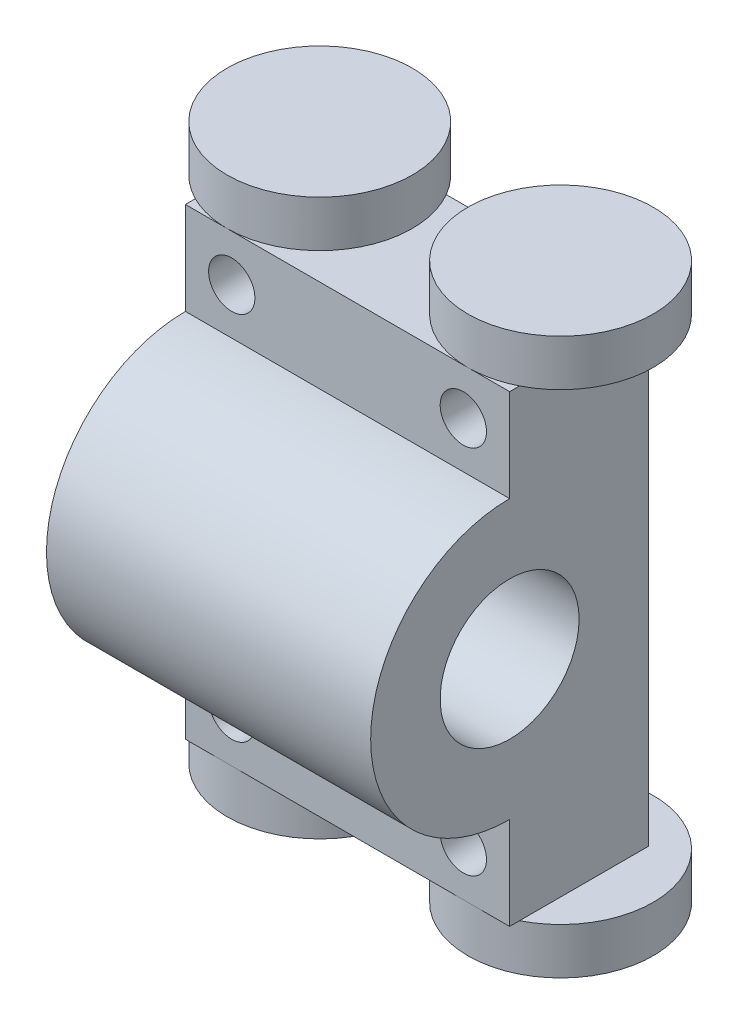
SolidWorks part; units mm, degrees
ref_plane "Front Plane" through (0, 0, 0) normal (0, 0, 1) x (1, 0, 0)
ref_plane "Top Plane" through (0, 0, 0) normal (0, 1, 0) x (1, 0, 0)
ref_plane "Right Plane" through (0, 0, 0) normal (1, 0, 0) x (0, 0, -1)
sketch "Sketch1" plane through (0, 0, 0) normal (1, 0, 0) x (0, 0, -1)
  line L5 (0, 0) -> (-30, 0) construction
  line L6 (-15, -15) -> (-15, -25)
  line L7 (-15, 25) -> (0, 25)
  line L8 (-15, 25) -> (-15, 15)
  line L9 (-15, -25) -> (0, -25)
  line L10 (0, 25) -> (0, -25)
  arc A0 (-15, 15) -> (-15, -15) centre (-15, 0) ccw
  point P0 (0, 0)
  point P1 (-29.8834, 0)
  point P2 (-15, -14.9995)
  point P3 (-15, -9.8928)
  point P9 (-32.7876, 0)
  point P15 (-28.8274, 0)
  point P16 (0, 0)
  dimension "D1" = 15
  dimension "D2" = 50
  dimension "D3" = 15
extrude "body" add sketch "Sketch1" along normal blind 35
sketch "Sketch3" plane through (35, 0, 0) normal (1, 0, 0) x (0, 0, -1)
  circle A0 centre (-15, 0) radius 7.5
  arc A1 (-15, 15) -> (-15, -15) centre (-15, 0) ccw construction
  dimension "D1" = 15
extrude "shaft hole" cut sketch "Sketch3" against normal blind 40
sketch "Sketch4" plane through (0, 25, 0) normal (0, 1, 0) x (1, 0, 0)
  line L0 (17.5, -15) -> (17.5, -6.3939) construction
  line L3 (35, 0) -> (0, 0) construction
  circle A0 centre (4.5, -5) radius 2.5
  circle A1 centre (30.5, -5) radius 2.5
  point P6 (0, 0)
  point P9 (17.5, 0)
  point P10 (7.2598, -4.9505)
  point P11 (7.5, -14.6293)
  point P12 (17.5, -6.3939)
  dimension "D1" = 5
  dimension "D2" = 26
  dimension "D3" = 5
extrude "Boss-Extrude1" add sketch "Sketch4" along normal blind 5
mirror "Mirror1" about plane through (0, 0, 0) normal (0, 1, 0) of "Boss-Extrude1"
sketch "Sketch5" plane through (0, 30, 0) normal (0, 1, 0) x (1, 0, 0)
  circle A0 centre (4.5, -5) radius 10
  dimension "D1" = 20
extrude "bearing" add sketch "Sketch5" against normal blind 5
mirror "Mirror2" about plane through (0, 0, 0) normal (0, 1, 0) of "bearing"
ref_plane "Plane1" through (17.5, 0, 0) normal (1, 0, 0) x (0, 0, -1)
mirror "Mirror5" about plane through (17.5, 0, 0) normal (1, 0, 0) of "bearing", "Mirror2"
sketch "Sketch6" plane through (0, 0, 15) normal (0, 0, 1) x (1, 0, 0)
  line L0 (30.5, 25) -> (4.5, 25) construction
  line L2 (0, 25) -> (0, 15) construction
  line L3 (17.5, 25) -> (17.5, -25) construction
  line L4 (30.5, -25) -> (4.5, -25) construction
  line L5 (0, 0) -> (35, 0) construction
  line L6 (35, -15) -> (35, 15) construction
  circle A0 centre (5, 20) radius 2.5
  circle A4 centre (30, 20) radius 2.5
  circle A5 centre (30, -20) radius 2.5
  circle A6 centre (5, -20) radius 2.5
  dimension "D1" = 5
  dimension "D2" = 5
  dimension "D3" = 5
extrude "Cut-Extrude1" cut sketch "Sketch6" against normal through all
